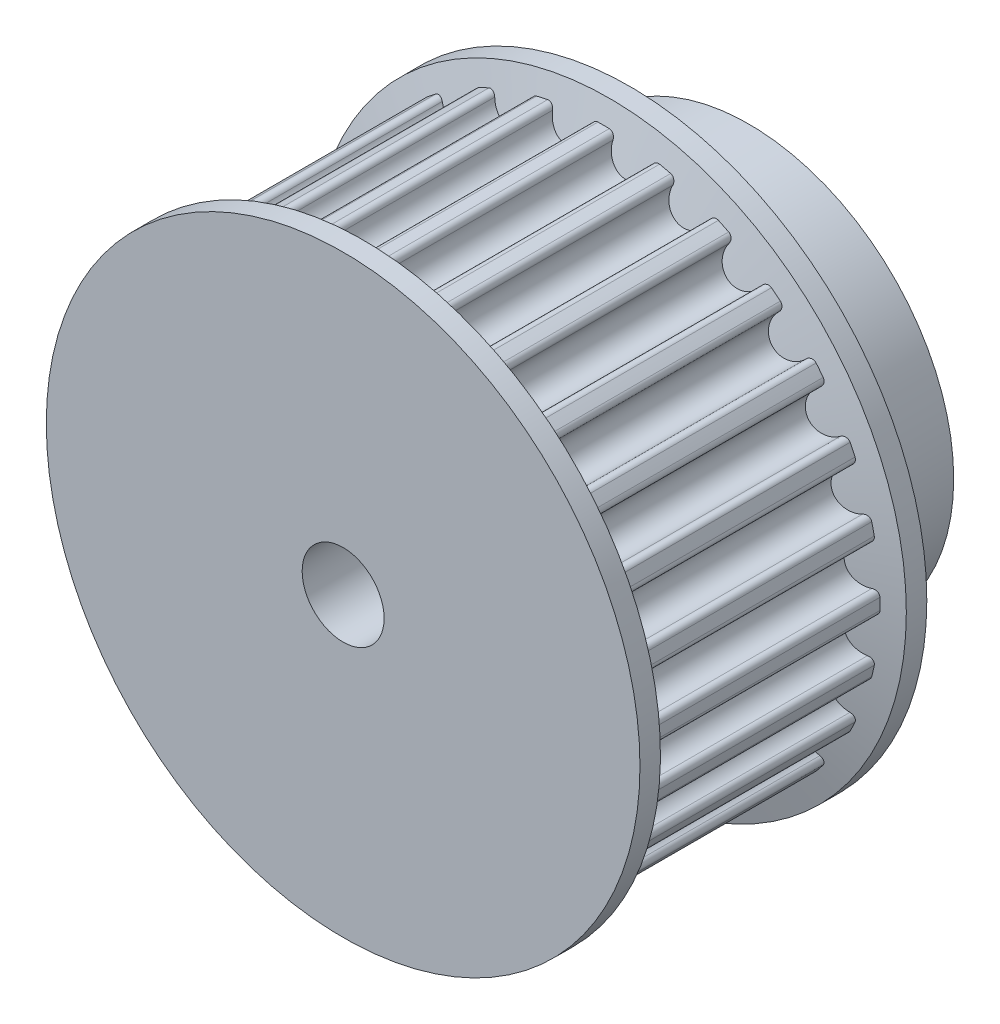
SolidWorks part; units mm, degrees
ref_plane "Front Plane" through (0, 0, 0) normal (0, 0, 1) x (1, 0, 0)
ref_plane "Top Plane" through (0, 0, 0) normal (0, 1, 0) x (1, 0, 0)
ref_plane "Right Plane" through (0, 0, 0) normal (1, 0, 0) x (0, 0, -1)
sketch "Sketch1" plane through (0, 0, 0) normal (0, 0, 1) x (1, 0, 0)
  circle A0 centre (0, 0) radius 22.2817
  dimension "D1" = 44.5634
extrude "Boss-Extrude1" add sketch "Sketch1" along normal mid plane 19.05
sketch "Sketch2" plane through (0, 0, 0) normal (0, 0, 1) x (1, 0, 0)
  line L0 (0, 0) -> (0, 21.4117) construction
  line L1 (0, 0) -> (2.3335, 20.7106) construction
  line L2 (0, 21.4117) -> (0, 22.2817)
  line L3 (2.3335, 20.7106) -> (2.4948, 22.1416) construction
  line L4 (4.7645, 20.8749) -> (4.9581, 21.723)
  arc A0 (0, 21.4117) -> (0.441, 21.4071) centre (0, 0) cw
  arc A1 (0.441, 21.4071) -> (0.858, 20.9175) centre (0.4321, 20.9772) cw
  arc A2 (0.858, 20.9175) -> (3.8181, 20.584) centre (2.3335, 20.7106) ccw
  circle A3 centre (0, 0) radius 22.2817 construction
  arc A4 (0, 22.2817) -> (4.9581, 21.723) centre (0, 0) cw
  arc A5 (4.3336, 20.9686) -> (3.8181, 20.584) centre (4.2466, 20.5475) ccw
  arc A6 (4.7645, 20.8749) -> (4.3336, 20.9686) centre (0, 0) ccw
  point P6 (2.1667, 19.23)
  dimension "D1" = 0.43
  dimension "D2" = 1.49
  dimension "D3" = 0.87
  dimension "D4" = 6.429
  dimension "D5" = 2.93
extrude "Cut-Extrude1" cut sketch "Sketch2" against normal through all both and the other way through all
pattern_circular "CirPattern1" count 28 over 360 about axis through (0, 0, 9.525) along (0, 0, -1) of "Cut-Extrude1" reverse direction yes
sketch "Sketch4" plane through (0, 0, 9.525) normal (0, 0, 1) x (1, 0, 0)
  circle A0 centre (0, 0) radius 22.9992
  arc A1 (20.7723, -5.1935) -> (20.9686, -4.3336) centre (0, 0) ccw construction
  circle A2 centre (0, 0) radius 3.175
  dimension "D1" = 1.5875
  dimension "D2" = 6.35
extrude "Boss-Extrude2" add sketch "Sketch4" along normal blind 1.5875
sketch "Sketch3" plane through (0, 0, 11.1125) normal (0, 0, 1) x (1, 0, 0)
  circle A0 centre (0, 0) radius 3.175
  dimension "D1" = 6.35
extrude "Cut-Extrude2" cut sketch "Sketch3" against normal through all both and the other way through all
sketch "Sketch6" plane through (0, 0, 0) normal (0, 1, 0) x (1, 0, 0)
  line L0 (22.9992, -9.525) -> (18.542, -8.255)
  line L1 (18.542, -8.255) -> (18.542, -9.525)
  line L2 (20.2022, -9.525) -> (18.1821, -9.525) construction
  line L3 (18.542, -9.525) -> (22.9992, -9.525)
  dimension "D1" = 18.542
  dimension "D2" = 1.27
ref_axis "Axis1" through (0, 0, -9.525) along (0, 0, 1)
revolve "Revolve1" add sketch "Sketch6" angle 360 about axis through (0, 0, -9.525) along (0, 0, 1)
mirror "Mirror1" about plane through (0, 0, 0) normal (0, 0, 1) of "Boss-Extrude2", "Revolve1"
sketch "Sketch8" plane through (0, 0, -11.1125) normal (0, 0, -1) x (-1, 0, 0)
  circle A0 centre (0, 0) radius 15.875
  circle A1 centre (0, 0) radius 3.175 construction
  circle A2 centre (0, 0) radius 3.175
  dimension "D1" = 31.75
extrude "Boss-Extrude3" add sketch "Sketch8" along normal blind 9.2075
sketch "Sketch9" plane through (0, 0, -20.32) normal (0, 0, -1) x (-1, 0, 0)
  line L0 (0, -3.175) -> (0, -11.43) construction
  line L1 (0, -11.43) -> (-4.7625, -11.43) construction
  line L2 (0, -11.43) -> (4.7625, -11.43) construction
  line L4 (4.7625, -5.08) -> (-4.7625, -5.08)
  line L5 (4.7625, -5.08) -> (4.7625, -11.43)
  line L6 (4.7625, -11.43) -> (-4.7625, -11.43)
  line L7 (-4.7625, -5.08) -> (-4.7625, -11.43)
  line L8 (4.7625, -5.08) -> (-4.7625, -11.43) construction
  line L9 (4.7625, -11.43) -> (-4.7625, -5.08) construction
  circle A0 centre (0, 0) radius 3.175 construction
  point P9 (0, -8.255)
  dimension "D1" = 6.35
  dimension "D2" = 9.525
  dimension "D3" = 8.255
ref_plane "Plane1" through (0, -5.08, 0) normal (0, -1, 0) x (1, 0, 0)
sketch "Sketch10" plane through (0, -5.08, 0) normal (0, -1, 0) x (1, 0, 0)
  line L0 (0, -20.32) -> (0, -16.7005) construction
  line L1 (-22.9992, -11.1125) -> (22.9992, -11.1125) construction
  line L2 (-2.8596, -21.6535) -> (2.8596, -21.6535) construction
  line L3 (2.8596, -21.6535) -> (5.7192, -16.7005) construction
  line L4 (5.7192, -16.7005) -> (2.8596, -11.7475)
  line L5 (2.8596, -11.7475) -> (-2.8596, -11.7475)
  line L6 (-2.8596, -11.7475) -> (-5.7192, -16.7005)
  line L7 (-5.7192, -16.7005) -> (-2.8596, -21.6535) construction
  line L8 (5.7192, -16.7005) -> (5.7192, -24.8285)
  line L9 (5.7192, -24.8285) -> (-5.7192, -24.8285)
  line L10 (-5.7192, -24.8285) -> (-5.7192, -16.7005)
  line L11 (-15.875, -20.32) -> (15.875, -20.32) construction
  circle A0 centre (0, -16.7005) radius 4.953 construction
  circle A1 centre (0, -16.7005) radius 2.54
  circle A2 centre (0, -16.7005) radius 5.588 construction
  point P15 (0, -15.113)
  dimension "D2" = 5.08
  dimension "D3" = 3.6195
  dimension "D1" = 9.906
  dimension "D4" = 3.175
extrude "Cut-Extrude3" cut sketch "Sketch10" along normal up to vertex (6.35 mm away) contours L5 L6 L10 L9 L8 L4 up to point (4.7625, -11.43, -20.32)
extrude "Cut-Extrude4" cut sketch "Sketch10<3>" against normal blind 4.572 and the other way through all contours A1
sketch "Sketch10<3>" plane through (0, -5.08, 0) normal (0, -1, 0) x (1, 0, 0) same geometry as "Sketch10"
equation "\"n\"= 28'Number of Teeth"
equation "\"p\"= 5mm'Pitch"
equation "\"pd\"= \"n\" * \"p\" / pi'Pitch Diameter"
equation "\"D1@Sketch1\"=\"pd\""
equation "\"w\"= 0.75'Pulley Width"
equation "\"D1@Boss-Extrude1\"=\"w\""
equation "\"D4@Sketch2\"=180/\"n\""
equation "\"D1@CirPattern1\"=\"n\""
